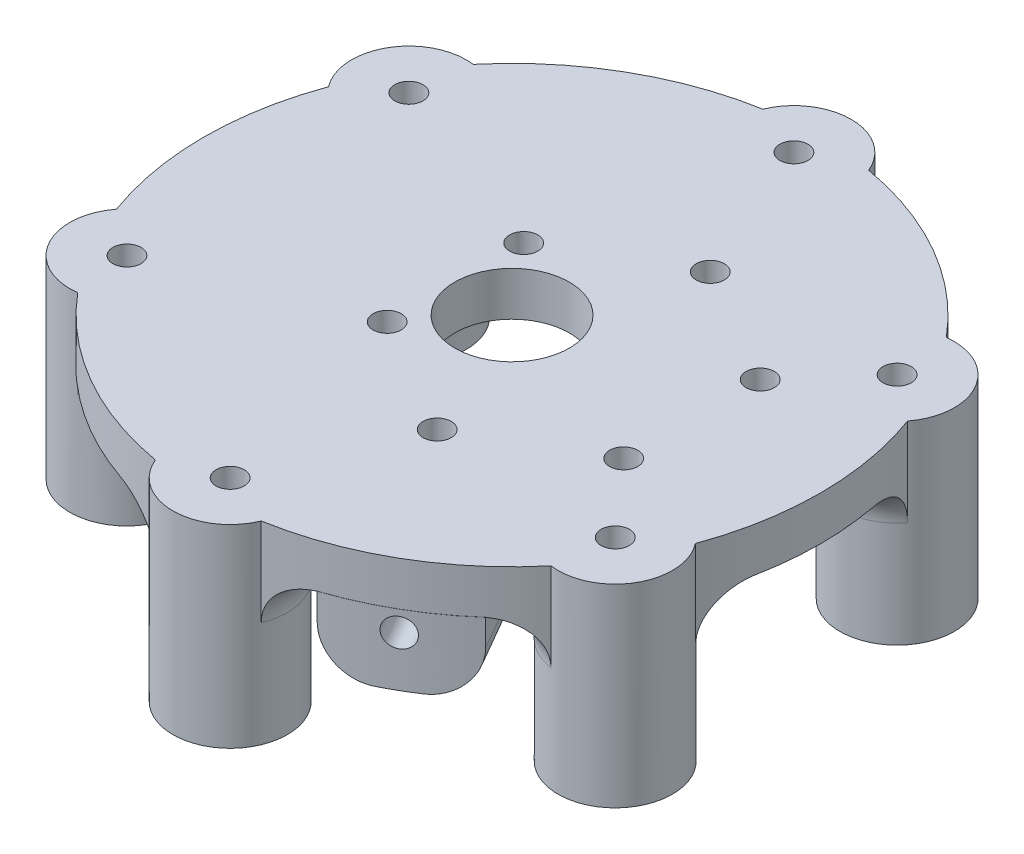
SolidWorks part; units mm, degrees
material "PET"
ref_plane "Спереди" through (0, 0, 0) normal (0, 0, 1) x (1, 0, 0)
ref_plane "Сверху" through (0, 0, 0) normal (0, 1, 0) x (1, 0, 0)
ref_plane "Справа" through (0, 0, 0) normal (1, 0, 0) x (0, 0, -1)
sketch "Эскиз1" plane through (0, 0, 0) normal (0, 1, 0) x (1, 0, 0)
  line L0 (0, 0) -> (-88.443, 0) construction
  line L1 (0, 0) -> (37.8496, 0) construction
  line L2 (-34.187, 7.5) -> (-27.187, 7.5) construction
  line L3 (-34.187, 7.5) -> (-34.187, -7.5) construction
  line L4 (-34.187, -7.5) -> (-27.187, -7.5) construction
  line L5 (-27.187, 7.5) -> (-27.187, -7.5) construction
  line L6 (20.0887, 19.7946) -> (7.0983, 27.2946) construction
  line L7 (23.5887, 25.8568) -> (20.0887, 19.7946) construction
  line L8 (23.5887, 25.8568) -> (10.5983, 33.3568) construction
  line L9 (10.5983, 33.3568) -> (7.0983, 27.2946) construction
  line L10 (7.0983, -27.2946) -> (20.0887, -19.7946) construction
  line L11 (10.5983, -33.3568) -> (7.0983, -27.2946) construction
  line L12 (10.5983, -33.3568) -> (23.5887, -25.8568) construction
  line L13 (23.5887, -25.8568) -> (20.0887, -19.7946) construction
  line L14 (-0.0002, -32) -> (0, -32.0001)
  line L16 (-27.7129, -16) -> (-27.7127, -16.0001)
  line L17 (0, -32.0001) -> (0.0002, -32)
  line L18 (27.7129, -16) -> (27.7129, -15.9999)
  line L19 (27.7129, 16) -> (27.7127, 16.0001)
  line L20 (0, 32.0001) -> (-0.0002, 32)
  line L22 (-27.7129, -15.9999) -> (-27.7129, -16)
  line L23 (-27.7127, 16.0001) -> (-27.7129, 16)
  line L24 (-27.7129, 16) -> (-27.7129, 15.9999) [skipped]
  line L25 (0.0002, 32) -> (0, 32.0001)
  line L26 (27.7129, 15.9999) -> (27.7129, 16)
  line L27 (27.7127, -16.0001) -> (27.7129, -16)
  arc A0 (6.0081, -34.4805) -> (26.8569, -22.4434) centre (0, 0) ccw
  circle A1 centre (0, 0) radius 6.5
  circle A3 centre (7, 15.5) radius 1.6
  circle A4 centre (20.4234, 7.75) radius 1.6
  circle A5 centre (20.4234, -7.75) radius 1.6
  circle A6 centre (7, -15.5) radius 1.6
  circle A7 centre (-6.4234, -7.75) radius 1.6
  circle A8 centre (-6.4234, 7.75) radius 1.6
  circle A10 centre (7, 0) radius 18.5 construction
  circle A11 centre (0, 0) radius 32 construction
  circle A12 centre (0, 0) radius 27.7129 construction
  circle A13 centre (-27.7129, -16) radius 1.6
  circle A14 centre (-27.7129, 16) radius 1.6
  circle A15 centre (0, 32.0001) radius 1.6
  circle A16 centre (27.7129, 16) radius 1.6
  circle A17 centre (27.7129, -16) radius 1.6
  circle A18 centre (0, -32.0001) radius 1.6
  arc A19 (26.8569, -22.4434) -> (32.865, -12.037) centre (27.7129, -16) ccw
  arc A20 (-6.0081, -34.4805) -> (6.0081, -34.4805) centre (0, -32.0001) ccw
  arc A21 (-32.865, -12.037) -> (-26.8569, -22.4434) centre (-27.7129, -16) ccw
  arc A23 (6.0081, 34.4805) -> (-6.0081, 34.4805) centre (0, 32.0001) ccw
  arc A25 (32.865, -12.037) -> (32.865, 12.037) centre (0, 0) ccw
  arc A26 (-26.8569, -22.4434) -> (-6.0081, -34.4805) centre (0, 0) ccw
  arc A27 (-26.8569, 22.4434) -> (-32.865, 12.037) centre (-27.7129, 16) ccw
  arc A28 (-30.3743, 10.0699) -> (-25.9427, 9.7457) centre (-27.7129, 16) ccw [skipped]
  arc A29 (-32.865, 12.037) -> (-32.865, -12.037) centre (0, 0) ccw
  arc A30 (-6.0081, 34.4805) -> (-26.8569, 22.4434) centre (0, 0) ccw
  arc A31 (32.865, 12.037) -> (26.8569, 22.4434) centre (27.7129, 16) ccw
  arc A32 (23.9079, 21.27) -> (21.4114, 17.5942) centre (27.7129, 16) ccw [skipped]
  arc A33 (26.8569, 22.4434) -> (6.0081, 34.4805) centre (0, 0) ccw
  point P21 (7, 0)
  point P24 (-27.187, 0)
  point P37 (0, 0)
  point P56 (0, 0)
  point P81 (0, 0)
  dimension "D1" = 70
  dimension "D2" = 13
  dimension "D3" = 7
  dimension "D5" = 3.2
  dimension "D4" = 37
  dimension "D9" = 64
  dimension "D10" = 3.2
  dimension "D12" = 13
  dimension "D7" = 15
  dimension "D6" = 6
  dimension "D8" = 3
  dimension "D11" = 6
  dimension "D13" = 6
extrude "Бобышка-Вытянуть1" add sketch "Эскиз1" along normal blind 5 contours A26 A20 A0 A19 A25 A31 A33 A23 A30 A27 A29 A21 | A7 | A6 | A5 | A4 | A3 | A8 | A1 | A18 | A17 | A16 | A15 | A14 | A13
sketch "Эскиз2" plane through (0, 0, 0) normal (0, -1, 0) x (1, 0, 0)
  line L5 (0, 0) -> (25.0528, -43.3927) construction
  line L6 (0, 0) -> (50.3764, 0) construction
  line L8 (11.0921, -33.212) -> (7.9455, -27.762)
  line L9 (7.9455, -27.762) -> (20.0698, -20.762)
  line L10 (20.0698, -20.762) -> (23.2164, -26.212)
  line L11 (-34.3085, 7) -> (-28.0153, 7)
  line L12 (-28.0153, 7) -> (-28.0153, -7)
  line L13 (-28.0153, -7) -> (-34.3085, -7)
  line L14 (23.2164, 26.212) -> (20.0698, 20.762)
  line L15 (20.0698, 20.762) -> (7.9455, 27.762)
  line L16 (7.9455, 27.762) -> (11.0921, 33.212)
  circle A0 centre (0, 0) radius 35.0153 construction
  arc A1 (11.0921, -33.212) -> (23.2164, -26.212) centre (0, 0) ccw
  arc A2 (-34.3085, 7) -> (-34.3085, -7) centre (0, 0) ccw
  arc A3 (23.2164, 26.212) -> (11.0921, 33.212) centre (0, 0) ccw
  point P20 (0, 0)
  dimension "D1" = 3
  dimension "D2" = 60
extrude "Бобышка-Вытянуть2" add sketch "Эскиз2" along normal blind 8
sketch "Эскиз3" plane through (-28.0153, 0, 0) normal (1, 0, 0) x (0, 0, -1)
  line L0 (-8.5188, 5) -> (8.83, 5) construction
  line L1 (12.037, 5) -> (-12.037, 5) construction
  line L2 (0, 0) -> (0, -13.7312) construction
  circle A0 centre (0, -2.3) radius 1.6
  point P9 (0.1556, 5)
  dimension "D1" = 3.2
  dimension "D2" = 7.3
extrude "Вырез-Вытянуть1" cut sketch "Эскиз3" against normal through all
pattern_circular "Круговой массив1" count 3 over 360 about axis through (0, 5, 0) along (0, 1, 0) of "Вырез-Вытянуть1"
fillet "Скругление1" radius 5 6 edges at (-31.1619, -8, 7) (-31.1619, -8, -7) (9.5188, -8, -30.487) (21.6431, -8, -23.487) (21.6431, -8, 23.487) (9.5188, -8, 30.487)
fillet "Скругление2" radius 3 3 edges at (14.0077, 0, -24.262) (14.0077, 0, 24.262) (-28.0153, 0, 0)
sketch "Эскиз5" plane through (-28.0153, 0, 0) normal (1, 0, 0) x (0, 0, -1)
  circle A0 centre (0, -2.3) radius 3
  dimension "D1" = 6
extrude "Вырез-Вытянуть2" cut sketch "Эскиз5" along normal blind 7
pattern_circular "Круговой массив2" count 3 over 360 about axis through (0, 0, 0) along (0, 1, 0) of "Вырез-Вытянуть2"
fillet "Скругление3" radius 1 3 edges at (10.5077, 0, 18.1998) (-21.0153, 0, 0) (10.5077, 0, -18.1998)
sketch "Эскиз6" plane through (0, 0, 0) normal (0, -1, 0) x (1, 0, 0)
  circle A0 centre (-27.7129, -16) radius 6.5
  circle A1 centre (-27.7129, 16) radius 6.5
  circle A2 centre (0, 32.0001) radius 6.5
  circle A3 centre (27.7129, 16) radius 6.5
  circle A4 centre (27.7129, -16) radius 6.5
  circle A5 centre (0, -32.0001) radius 6.5
  point P15 (0, 0)
  dimension "D1" = 6
extrude "Бобышка-Вытянуть4" add sketch "Эскиз6" along normal blind 17
sketch "Эскиз8" plane through (0, -17, 0) normal (0, -1, 0) x (1, 0, 0)
  line L0 (24.9129, -14.3835) -> (24.9129, -17.6166)
  line L1 (24.9129, 14.3835) -> (27.7129, 12.7669)
  line L2 (27.7129, 12.7669) -> (30.5129, 14.3835)
  line L3 (30.5129, 14.3835) -> (30.5129, 17.6166)
  line L4 (30.5129, 17.6166) -> (27.7129, 19.2332)
  line L5 (27.7129, 19.2332) -> (24.9129, 17.6166)
  line L6 (24.9129, 17.6166) -> (24.9129, 14.3835)
  line L7 (27.7129, -12.7669) -> (24.9129, -14.3835)
  line L8 (30.5129, -14.3835) -> (27.7129, -12.7669)
  line L9 (30.5129, -17.6166) -> (30.5129, -14.3835)
  line L10 (27.7129, -19.2332) -> (30.5129, -17.6166)
  line L11 (24.9129, -17.6166) -> (27.7129, -19.2332)
  line L12 (0, -28.7669) -> (-2.8, -30.3835)
  line L13 (2.8, -30.3835) -> (0, -28.7669)
  line L14 (2.8, -33.6167) -> (2.8, -30.3835)
  line L15 (0, -35.2333) -> (2.8, -33.6167)
  line L16 (-2.8, -33.6167) -> (0, -35.2333)
  line L17 (-2.8, -30.3835) -> (-2.8, -33.6167)
  line L18 (-24.9129, -14.3835) -> (-27.7129, -12.7669)
  line L19 (-24.9129, -17.6166) -> (-24.9129, -14.3835)
  line L20 (-27.7129, -19.2332) -> (-24.9129, -17.6166)
  line L21 (-30.5129, -17.6166) -> (-27.7129, -19.2332)
  line L22 (-30.5129, -14.3835) -> (-30.5129, -17.6166)
  line L23 (-27.7129, -12.7669) -> (-30.5129, -14.3835)
  line L24 (-24.9129, 14.3835) -> (-24.9129, 17.6166)
  line L25 (-27.7129, 12.7669) -> (-24.9129, 14.3835)
  line L26 (-30.5129, 14.3835) -> (-27.7129, 12.7669)
  line L27 (-30.5129, 17.6166) -> (-30.5129, 14.3835)
  line L28 (-27.7129, 19.2332) -> (-30.5129, 17.6166)
  line L29 (-24.9129, 17.6166) -> (-27.7129, 19.2332)
  line L30 (0, 28.7669) -> (2.8, 30.3835)
  line L31 (-2.8, 30.3835) -> (0, 28.7669)
  line L32 (-2.8, 33.6167) -> (-2.8, 30.3835)
  line L33 (0, 35.2333) -> (-2.8, 33.6167)
  line L34 (2.8, 33.6167) -> (0, 35.2333)
  line L35 (2.8, 30.3835) -> (2.8, 33.6167)
  circle A0 centre (27.7129, 16) radius 2.8 construction
  point P41 (0, 0)
  dimension "D1" = 5.6
  dimension "D2" = 6
extrude "Вырез-Вытянуть3" cut sketch "Эскиз8" against normal blind 5
sketch "Эскиз9" plane through (0, 5, 0) normal (0, 1, 0) x (1, 0, 0)
  circle A0 centre (-27.7129, 16) radius 1.6
  circle A1 centre (0, 32.0001) radius 1.6
  circle A2 centre (27.7129, 16) radius 1.6
  circle A3 centre (27.7129, -16) radius 1.6
  circle A4 centre (0, -32.0001) radius 1.6
  circle A5 centre (-27.7129, -16) radius 1.6
extrude "Вырез-Вытянуть4" cut sketch "Эскиз9" against normal through all
fillet "Скругление5" radius 5 6 edges at (0, 0, -25.5001) (22.0837, 0, -12.75) (22.0837, 0, 12.75) (0, 0, 25.5001) (-22.0837, 0, 12.75) (-22.0837, 0, -12.75)
sketch "Эскиз10" plane through (0, 0, 0) normal (0, -1, 0) x (1, 0, 0)
  circle A0 centre (7, 15.5) radius 1.6
  circle A1 centre (7, -15.5) radius 1.6
  circle A2 centre (7, 0) radius 19
  dimension "D1" = 38
extrude "Вырез-Вытянуть5" cut sketch "Эскиз10" along normal blind 5
